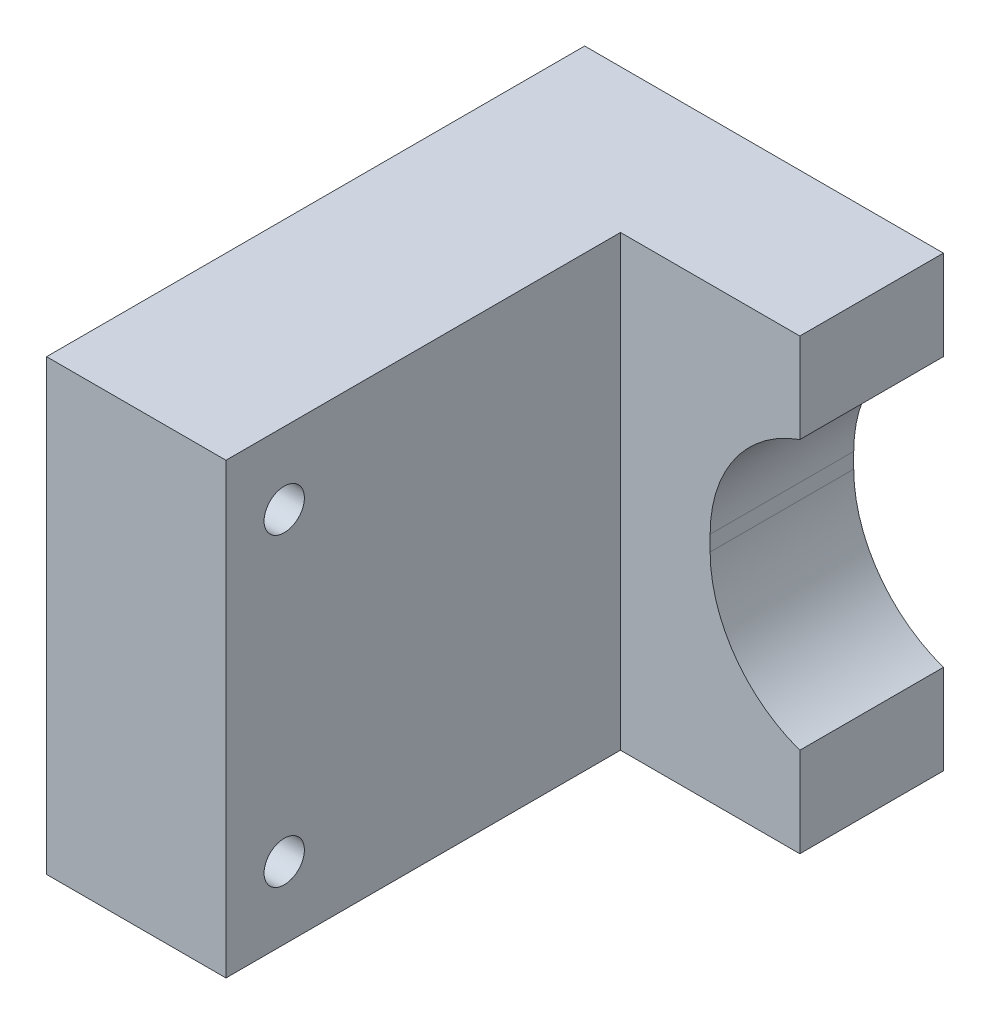
SolidWorks part; units mm, degrees
ref_plane "Front Plane" through (0, 0, 0) normal (0, 0, 1) x (1, 0, 0)
ref_plane "Top Plane" through (0, 0, 0) normal (0, 1, 0) x (1, 0, 0)
ref_plane "Right Plane" through (0, 0, 0) normal (1, 0, 0) x (0, 0, -1)
sketch "Sketch3" plane through (0, 0, 0) normal (0, 1, 0) x (1, 0, 0)
  line L1 (10, -30) -> (-10, -30)
  line L2 (10, -30) -> (10, 30)
  line L3 (10, 30) -> (-10, 30)
  line L4 (-10, -30) -> (-10, 30)
  line L5 (10, -30) -> (-10, 30) construction
  line L6 (10, 30) -> (-10, -30) construction
  line L7 (10, 30) -> (30, 30)
  line L8 (10, 30) -> (10, 13.9904)
  line L9 (10, 13.9904) -> (30, 13.9904)
  line L10 (30, 30) -> (30, 13.9904)
  point P0 (0, 0)
  dimension "D1" = 60
  dimension "D2" = 20
  dimension "D3" = 20
extrude "Boss-Extrude1" add sketch "Sketch3" along normal blind 50 contours L4 L1 L2 L3 | L10 L7 L2 L9 region at (0, 0, 0) region at (20, 0, -21.9952)
sketch "Sketch4" plane through (30, 0, 0) normal (1, 0, 0) x (0, 0, -1)
  line L0 (13.9904, 50) -> (13.9904, 0) construction
  line L1 (13.9904, 40) -> (30, 40)
  line L2 (13.9904, 40) -> (13.9904, 10)
  line L3 (13.9904, 10) -> (30, 10)
  line L4 (30, 40) -> (30, 10)
  line L5 (30, 50) -> (30, 0) construction
  dimension "D1" = 30
  dimension "D2" = 10
extrude "Cut-Extrude1" cut sketch "Sketch4" against normal blind 10
fillet "Fillet4" radius 15 2 edges at (20, 10, -21.9952) (20, 40, -21.9952)
hole_wizard "CSK for #8 Flat Head Machine Screw (100)1" positions "Sketch5" profile "Sketch6" countersink size "#8" standard "ANSI Inch" end condition up to next
sketch "Sketch5" plane through (-10, 0, 0) normal (-1, 0, 0) x (0, 0, 1)
  line L0 (30, 0) -> (-30, 0) construction
  line L1 (30, 50) -> (30, 0) construction
  line L2 (30, 50) -> (-30, 50) construction
  point P0 (23.5, 8)
  point P2 (23.5, 42)
  dimension "D1" = 8
  dimension "D2" = 6.5
  dimension "D3" = 6.5
  dimension "D4" = 8
sketch "Sketch6" plane through (-10, 8, 23.5) normal (0, 1, 0) x (0, 0, 1)
  line L0 (0, 0) -> (0, 20)
  line L1 (0, 20) -> (2.2479, 20)
  line L2 (2.2479, 20) -> (2.2479, 1.6518)
  line L3 (2.2479, 1.6518) -> (4.2164, 0)
  line L5 (4.2164, 0) -> (0, 0)
  line L6 (-2.2479, 1.6518) -> (-4.2164, 0) construction
  line L11 (0, -6.35) -> (0, 107.95) construction
  dimension "Thru Hole Dia." = 4.4958
  dimension "Thru Hole Depth" = 20
  dimension "Near C'Sink Dia." = 8.4328
  dimension "Near C'Sink Angle" = 100
